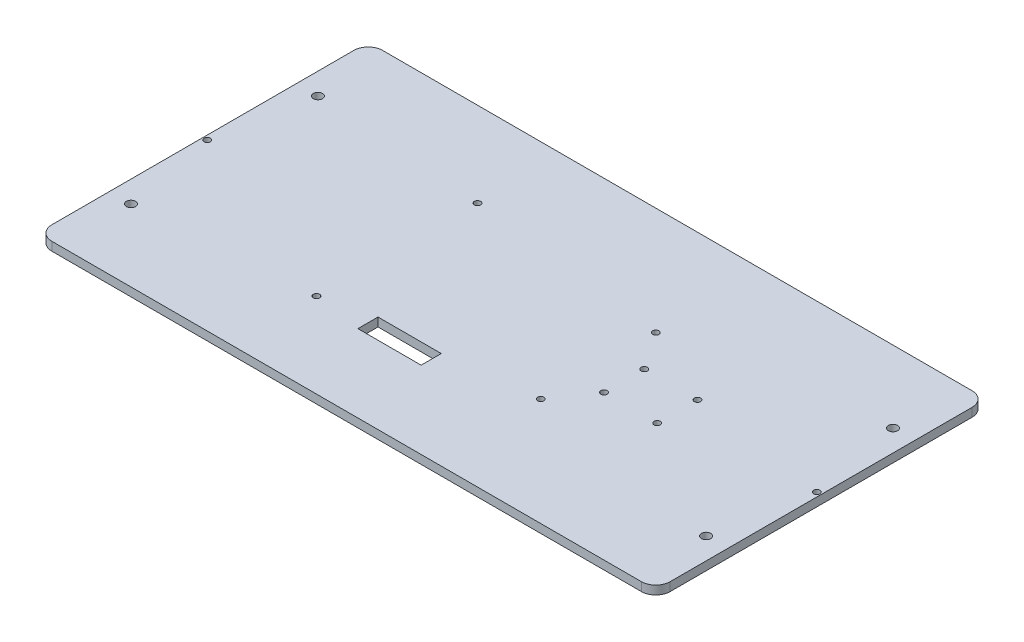
SolidWorks part; units mm, degrees
ref_plane "Front Plane" through (0, 0, 0) normal (0, 0, 1) x (1, 0, 0)
ref_plane "Top Plane" through (0, 0, 0) normal (0, 1, 0) x (1, 0, 0)
ref_plane "Right Plane" through (0, 0, 0) normal (1, 0, 0) x (0, 0, -1)
sketch "Sketch1" plane through (0, 0, 0) normal (0, 1, 0) x (1, 0, 0)
  line L0 (-107.5, 0) -> (107.5, 0) construction
  line L1 (-107.5, -57.5) -> (107.5, -57.5)
  line L2 (-107.5, -57.5) -> (-107.5, 57.5)
  line L3 (-107.5, 57.5) -> (107.5, 57.5)
  line L4 (107.5, -57.5) -> (107.5, 57.5)
  line L5 (-107.5, -57.5) -> (107.5, 57.5) construction
  line L6 (-107.5, 57.5) -> (107.5, -57.5) construction
  line L7 (0, 57.5) -> (0, -57.5) construction
  line L8 (-23, -23.6) -> (-1, -23.6)
  line L9 (-23, -23.6) -> (-23, -30.6)
  line L10 (-23, -30.6) -> (-1, -30.6)
  line L11 (-1, -23.6) -> (-1, -30.6)
  line L12 (-23, -23.6) -> (-1, -30.6) construction
  line L13 (-23, -30.6) -> (-1, -23.6) construction
  circle A0 centre (-40, 28) radius 1.1
  circle A1 centre (30, 20) radius 1.1
  circle A2 centre (-40, -28) radius 1.1
  circle A3 centre (30, -20) radius 1.1
  circle A4 centre (-100, 32.5) radius 1.6
  circle A5 centre (100, 32.5) radius 1.6
  circle A6 centre (100, -32.5) radius 1.6
  circle A7 centre (-100, -32.5) radius 1.6
  circle A9 centre (-106, 0) radius 1.1
  circle A11 centre (106, 0) radius 1.1
  circle A17 centre (39, 7) radius 1.1
  circle A18 centre (57.5, 7) radius 1.1
  circle A19 centre (57.5, -7) radius 1.1
  circle A20 centre (39, -7) radius 1.1
  point P0 (0, 0)
  point P16 (-12, -27.1)
  dimension "D3" = 2.2
  dimension "D5" = 2.2
  dimension "D13" = 3.2
  dimension "D16" = 1.5
  dimension "D17" = 2.2
  dimension "D18" = 2.2
  dimension "D20" = 18.5
  dimension "D21" = 2.2
  dimension "D1" = 115
  dimension "D2" = 215
  dimension "D4" = 28
  dimension "D6" = 70
  dimension "D7" = 8
  dimension "D8" = 40
  dimension "D9" = 7
  dimension "D10" = 22
  dimension "D11" = 28
  dimension "D12" = 0.9
  dimension "D14" = 7.5
  dimension "D15" = 25
  dimension "D19" = 1.5
  dimension "D22" = 7
  dimension "D23" = 50
extrude "Boss-Extrude1" add sketch "Sketch1" along normal blind 3
fillet "Fillet1" radius 5 4 edges at (-107.5, 1.5, -57.5) (107.5, 1.5, -57.5) (107.5, 1.5, 57.5) (-107.5, 1.5, 57.5)
